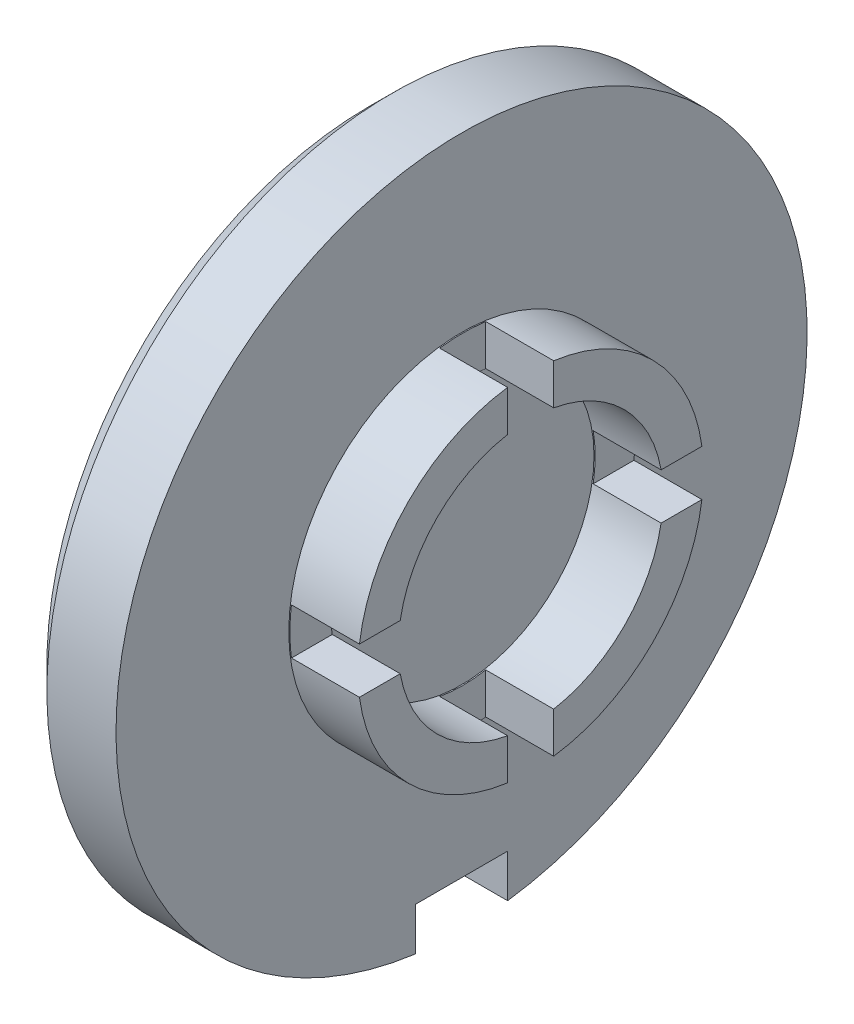
SolidWorks part; units mm, degrees
ref_plane "Front Plane" through (0, 0, 0) normal (0, 0, 1) x (1, 0, 0)
ref_plane "Top Plane" through (0, 0, 0) normal (0, 1, 0) x (1, 0, 0)
ref_plane "Right Plane" through (0, 0, 0) normal (1, 0, 0) x (0, 0, -1)
ref_plane "Plane1" through (0, 0, -52) normal (0, 0, 1) x (1, 0, 0)
sketch "Sketch1" plane through (0, 0, -52) normal (0, 0, 1) x (1, 0, 0)
  line L0 (-66, 18) -> (-53.2, 18) construction
  line L1 (-58.2, 20.3) -> (-59.4, 20.3)
  line L2 (-59.4, 20.3) -> (-59.4, 18)
  line L3 (-59.4, 18) -> (-61, 18)
  line L4 (-61, 18) -> (-61, 23.6)
  line L5 (-61, 23.6) -> (-60.6, 24)
  line L6 (-60.6, 24) -> (-59.4, 24)
  line L7 (-59.4, 24) -> (-59.4, 21)
  line L8 (-59.4, 21) -> (-58.2, 21)
  line L9 (-58.2, 21) -> (-58.2, 20.3)
revolve "Revolve1" add sketch "Sketch1" angle 360 about L0
sketch "Sketch2" plane through (0, 0, 0) normal (0, 0, 1) x (1, 0, 0)
  line L1 (-59.38, 17.6) -> (-58.1, 17.6)
  line L2 (-59.38, 17.6) -> (-59.38, 18.4)
  line L3 (-59.38, 18.4) -> (-58.1, 18.4)
  line L4 (-58.1, 17.6) -> (-58.1, 18.4)
extrude "Boss-Extrude1" add sketch "Sketch2" along normal blind 6.4 from offset 55.2 separate body offset against normal yes
combine bodies "Combine1" operation type subtract main body 101 bodies to subtract 102
sketch "Sketch3" plane through (0, 0, 0) normal (0, 0, 1) x (1, 0, 0)
  line L1 (-59.38, 14.8) -> (-58.1, 14.8)
  line L2 (-59.38, 14.8) -> (-59.38, 21.2)
  line L3 (-59.38, 21.2) -> (-58.1, 21.2)
  line L4 (-58.1, 14.8) -> (-58.1, 21.2)
extrude "Boss-Extrude2" add sketch "Sketch3" along normal blind 0.8 from offset 52.4 separate body offset against normal yes
combine bodies "Combine2" operation type subtract main body 103 bodies to subtract 104
sketch "Sketch4" plane through (0, 0, 0) normal (0, 0, 1) x (1, 0, 0)
  line L1 (-61.1, 11.9) -> (-59.3, 11.9)
  line L2 (-61.1, 11.9) -> (-61.1, 12.8)
  line L3 (-61.1, 12.8) -> (-59.3, 12.8)
  line L4 (-59.3, 11.9) -> (-59.3, 12.8)
extrude "Boss-Extrude3" add sketch "Sketch4" along normal blind 1.6 from offset 52.8 separate body offset against normal yes
combine bodies "Combine3" operation type subtract main body 105 bodies to subtract 106
